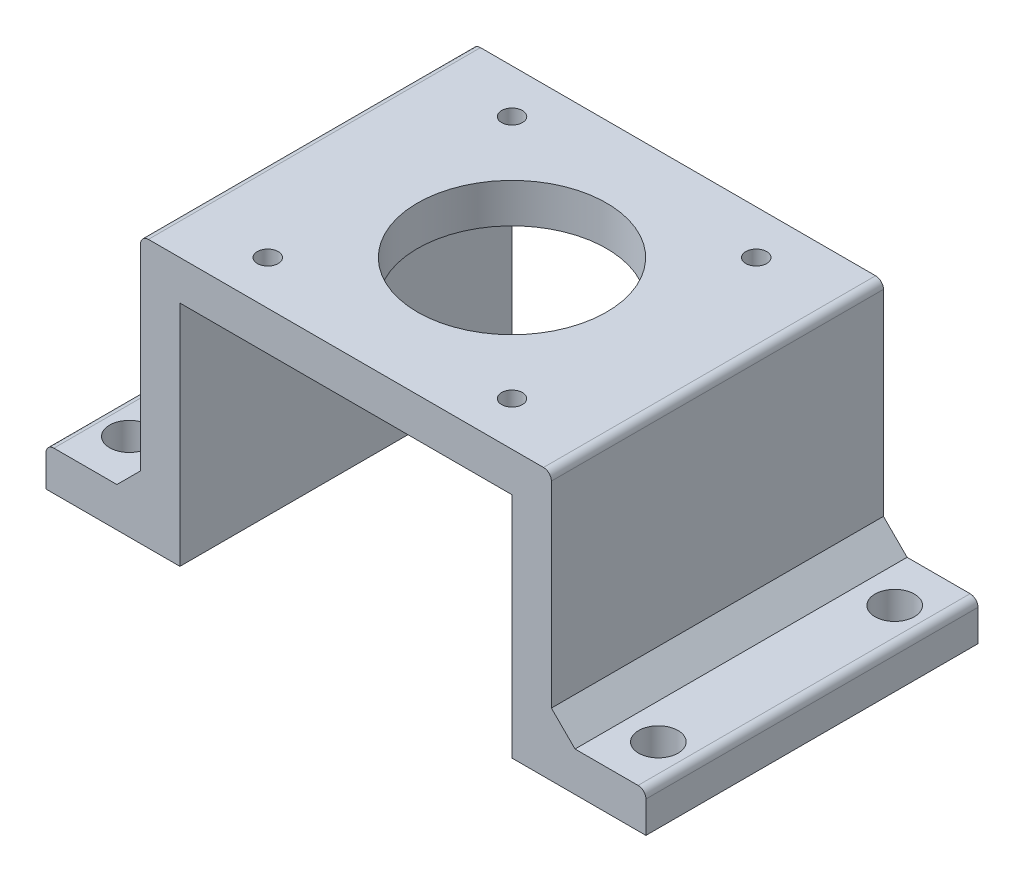
SolidWorks part; units mm, degrees
ref_plane "Plan de face" through (0, 0, 0) normal (0, 0, 1) x (1, 0, 0)
ref_plane "Plan de dessus" through (0, 0, 0) normal (0, 1, 0) x (1, 0, 0)
ref_plane "Plan de droite" through (0, 0, 0) normal (1, 0, 0) x (0, 0, -1)
sketch "Esquisse1" plane through (0, 0, 0) normal (0, 1, 0) x (1, 0, 0)
  line L1 (-21.075, -21.075) -> (21.075, -21.075)
  line L2 (-21.075, -21.075) -> (-21.075, 21.075)
  line L3 (-21.075, 21.075) -> (21.075, 21.075)
  line L4 (21.075, -21.075) -> (21.075, 21.075)
  line L5 (-21.075, -21.075) -> (21.075, 21.075) construction
  line L6 (-21.075, 21.075) -> (21.075, -21.075) construction
  point P0 (0, 0)
  dimension "D1" = 42.15
extrude "Boss.-Extru.1" add sketch "Esquisse1" along normal blind 5
sketch "Esquisse2" plane through (0, 5, 0) normal (0, 1, 0) x (1, 0, 0)
  line L0 (0, -19.1831) -> (0, 20.1838) construction
  line L1 (-17.0845, 0) -> (18.1385, 0) construction
  circle A1 centre (-15.5, 15.5) radius 1.325
  circle A2 centre (15.5, 15.5) radius 1.325
  dimension "D2" = 2.65
  dimension "D3" = 31
  dimension "D4" = 15.5
  dimension "D5" = 15.5
extrude "Enlèv. mat.-Extru.1" cut sketch "Esquisse2" against normal through all
mirror "Symétrie1" about plane through (0, 0, 0) normal (0, 0, 1) of "Enlèv. mat.-Extru.1"
sketch "Esquisse3" plane through (0, 5, 0) normal (0, 1, 0) x (1, 0, 0)
  circle A0 centre (0, 0) radius 12
  dimension "D1" = 24
extrude "Enlèv. mat.-Extru.2" cut sketch "Esquisse3" against normal through all
sketch "Esquisse4" plane through (21.075, 0, 0) normal (1, 0, 0) x (0, 0, -1)
  line L0 (21.075, 5) -> (21.075, 0) construction
  line L1 (-21.075, 5) -> (21.075, 5)
  line L2 (-21.075, 5) -> (-21.075, -28.95)
  line L3 (-21.075, -28.95) -> (21.075, -28.95)
  line L4 (21.075, 5) -> (21.075, -28.95)
  dimension "D1" = 33.95
extrude "Boss.-Extru.2" add sketch "Esquisse4" along normal blind 5
sketch "Esquisse5" plane through (26.075, 0, 0) normal (1, 0, 0) x (0, 0, -1)
  line L0 (21.075, -28.95) -> (21.075, 5) construction
  line L1 (-21.075, -28.95) -> (21.075, -28.95)
  line L2 (-21.075, -28.95) -> (-21.075, -23.95)
  line L3 (-21.075, -23.95) -> (21.075, -23.95)
  line L4 (21.075, -28.95) -> (21.075, -23.95)
  dimension "D1" = 5
extrude "Boss.-Extru.3" add sketch "Esquisse5" along normal blind 12
sketch "Esquisse7" plane through (0, -23.95, 0) normal (0, 1, 0) x (1, 0, 0)
  line L0 (38.075, 21.075) -> (38.075, -21.075) construction
  circle A0 centre (33.575, 15) radius 2.5
  circle A1 centre (33.575, -15) radius 2.5
  dimension "D1" = 5
  dimension "D2" = 30
  dimension "D3" = 15
  dimension "D4" = 4.5
extrude "Enlèv. mat.-Extru.3" cut sketch "Esquisse7" against normal through all
fillet "Congé2" radius 1 2 edges at (38.075, -23.95, 0) (26.075, 5, 0)
chamfer "Chanfrein1" distance 3 angle 45 1 edges at (26.075, -23.95, 0)
mirror "Symétrie3" about plane through (0, 0, 0) normal (1, 0, 0) of "Chanfrein1", "Congé2", "Enlèv. mat.-Extru.3", "Boss.-Extru.3", "Boss.-Extru.2"
